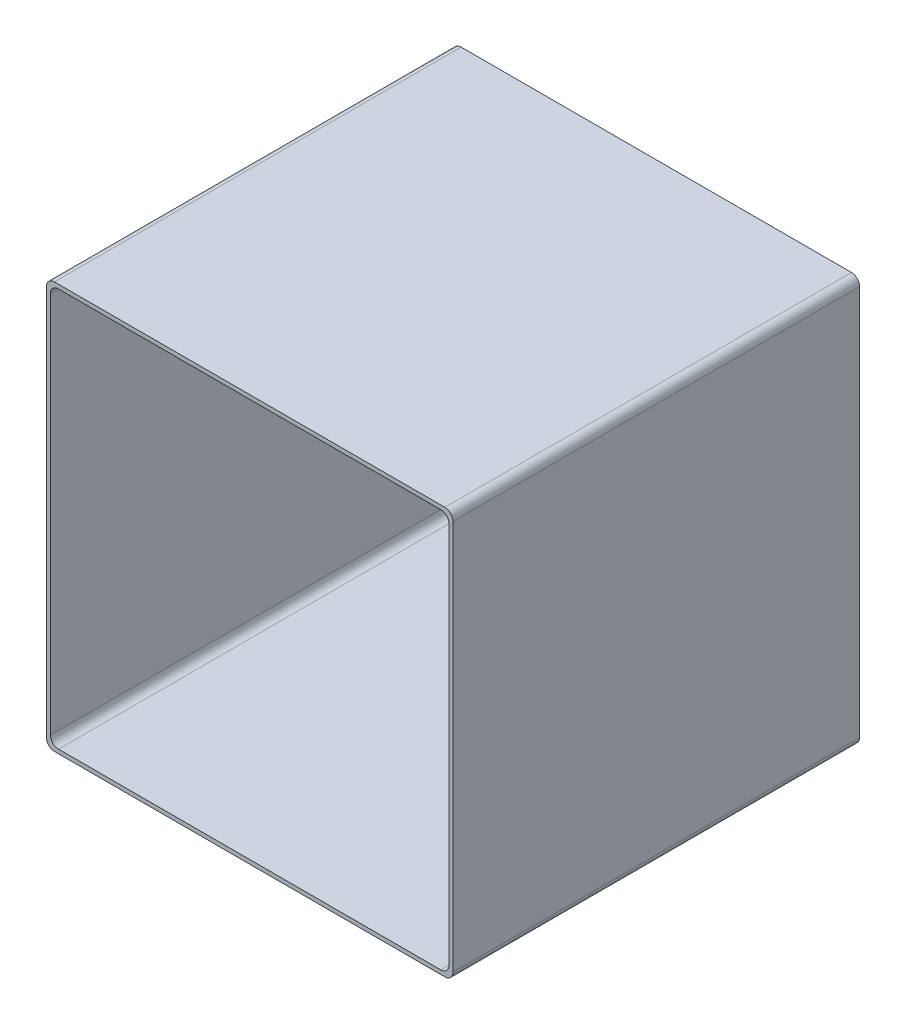
SolidWorks part; units mm, degrees
material "1060 Alloy"
ref_plane "Front Plane" through (0, 0, 0) normal (0, 0, 1) x (1, 0, 0)
ref_plane "Top Plane" through (0, 0, 0) normal (0, 1, 0) x (1, 0, 0)
ref_plane "Right Plane" through (0, 0, 0) normal (1, 0, 0) x (0, 0, -1)
sketch "Sketch2" plane through (0, 0, 0) normal (0, 0, 1) x (1, 0, 0)
  line L0 (0, 0) -> (500, 500) construction
  line L1 (0, 0) -> (500, 0)
  line L2 (0, 0) -> (0, 500)
  line L3 (0, 500) -> (500, 500)
  line L4 (500, 0) -> (500, 500)
  line L5 (5, 5) -> (495, 5)
  line L6 (5, 5) -> (5, 495)
  line L7 (5, 495) -> (495, 495)
  line L8 (495, 5) -> (495, 495)
  line L9 (0, 500) -> (500, 0) construction
  dimension "D1" = 500
  dimension "D2" = 500
  dimension "D3" = 5
extrude "Boss-Extrude1" add sketch "Sketch2" along normal blind 500
fillet "Fillet1" radius 10 8 edges at (495, 5, 250) (495, 495, 250) (5, 495, 250) (5, 5, 250) (0, 0, 250) (0, 500, 250) (500, 0, 250) (500, 500, 250)
